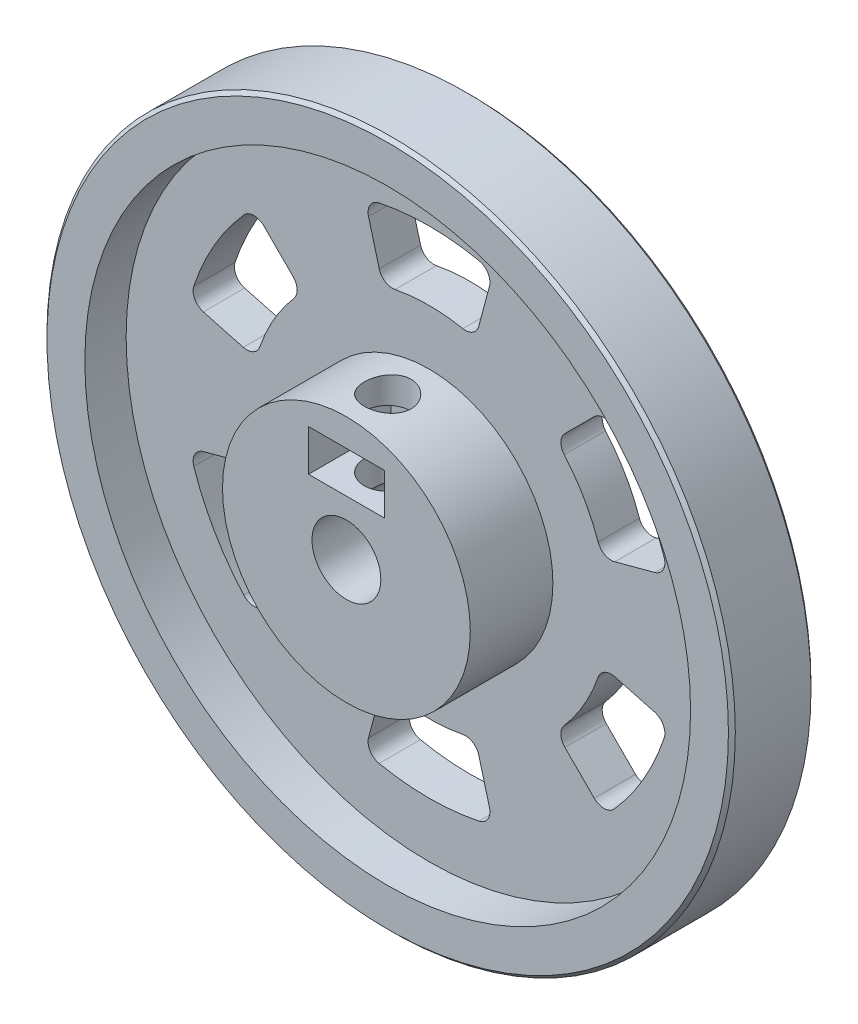
SolidWorks part; units mm, degrees
material "ABS"
ref_plane "Front Plane" through (0, 0, 0) normal (0, 0, 1) x (1, 0, 0)
ref_plane "Top Plane" through (0, 0, 0) normal (0, 1, 0) x (1, 0, 0)
ref_plane "Right Plane" through (0, 0, 0) normal (1, 0, 0) x (0, 0, -1)
sketch "Sketch1" plane through (0, 0, 0) normal (0, 0, 1) x (1, 0, 0)
  circle A0 centre (0, 0) radius 25
  dimension "D1" = 50
extrude "Boss-Extrude1" add sketch "Sketch1" along normal blind 3
sketch "Sketch3" plane through (0, 0, 0) normal (0, 0, 1) x (1, 0, 0)
  circle A0 centre (0, 0) radius 22
  circle A1 centre (0, 0) radius 25 construction
  circle A2 centre (0, 0) radius 25
  dimension "D1" = 3
extrude "Boss-Extrude3" add sketch "Sketch3" along normal blind 6
sketch "Sketch4" plane through (0, 0, 0) normal (0, 0, 1) x (1, 0, 0)
  circle A0 centre (0, 0) radius 9
  dimension "D1" = 18
extrude "Boss-Extrude4" add sketch "Sketch4" along normal blind 9
sketch "Sketch5" plane through (0, 0, 0) normal (0, 0, 1) x (1, 0, 0)
  circle A0 centre (0, 0) radius 2.5
  dimension "D1" = 5
extrude "Cut-Extrude1" cut sketch "Sketch5" along normal through all
sketch "Sketch6" plane through (0, 0, 9) normal (0, 0, 1) x (1, 0, 0)
  line L0 (0, 5.5) -> (0, 0) construction
  line L1 (-2.75, 7) -> (2.75, 7)
  line L2 (-2.75, 7) -> (-2.75, 4)
  line L3 (-2.75, 4) -> (2.75, 4)
  line L4 (2.75, 7) -> (2.75, 4)
  line L5 (-2.75, 7) -> (2.75, 4) construction
  line L6 (-2.75, 4) -> (2.75, 7) construction
  point P0 (0, 5.5)
  dimension "D1" = 3
  dimension "D2" = 5.5
  dimension "D3" = 5.5
extrude "Cut-Extrude2" cut sketch "Sketch6" against normal blind 6
sketch "Sketch7" plane through (0, 0, 0) normal (0, 1, 0) x (1, 0, 0)
  line L0 (0, 0) -> (0, -6) construction
  line L1 (2.75, -9) -> (-2.75, -9) construction
  circle A0 centre (0, -6) radius 1.7
  point P3 (0, -9)
  dimension "D2" = 3.4
  dimension "D1" = 3
extrude "Cut-Extrude3" cut sketch "Sketch7" along normal up to surface (9 mm away) up to face at (9, 0, 3)
sketch "Sketch8" plane through (0, 0, 0) normal (0, 0, 1) x (1, 0, 0)
  line L0 (0, 22) -> (0, 9) construction
  line L1 (0, 0) -> (-5.694, 21.2504) construction
  line L2 (-4.3923, 16.3923) -> (-3.6142, 13.4884)
  line L3 (0, 18) -> (0, 13) construction
  line L4 (4.3923, 16.3923) -> (3.6142, 13.4884)
  arc A0 (-3.6279, 17.6306) -> (3.6279, 17.6306) centre (0, 0) cw
  circle A1 centre (0, 0) radius 22 construction
  circle A2 centre (0, 0) radius 22 construction
  circle A3 centre (0, 0) radius 9 construction
  arc A4 (-2.4591, 12.7653) -> (2.4591, 12.7653) centre (0, 0) cw
  arc A5 (-2.4591, 12.7653) -> (-3.6142, 13.4884) centre (-2.6483, 13.7472) cw
  arc A6 (-3.6279, 17.6306) -> (-4.3923, 16.3923) centre (-3.4264, 16.6511) ccw
  arc A7 (2.4591, 12.7653) -> (3.6142, 13.4884) centre (2.6483, 13.7472) ccw
  arc A8 (3.6279, 17.6306) -> (4.3923, 16.3923) centre (3.4264, 16.6511) cw
  point P11 (0, 15.5)
  point P19 (-3.3646, 12.557)
  point P22 (-4.6587, 17.3867)
  point P23 (0, 15.5)
  dimension "D1" = 1
  dimension "D2" = 4
  dimension "D3" = 15
extrude "Cut-Extrude4" cut sketch "Sketch8" along normal through all
pattern_circular "CirPattern1" count 6 over 360 about axis through (0, 0, 9) along (0, 0, 1) of "Cut-Extrude4"
chamfer "Chamfer1" distance 0.25 angle 45 2 edges at (25, 0, 6) (25, 0, 0)
ref_plane "Plane1" through (0, 0, 3) normal (0, 0, 1) x (1, 0, 0)
